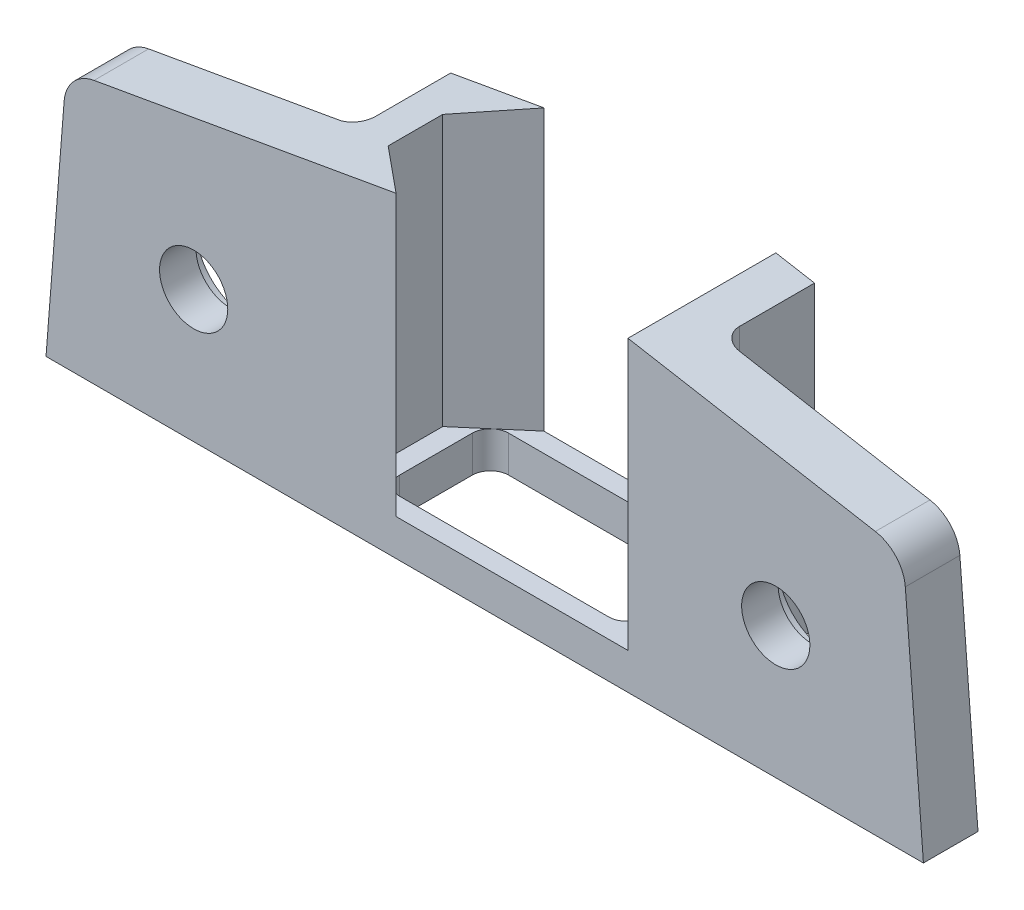
SolidWorks part; units mm, degrees
ref_plane "Front Plane" through (0, 0, 0) normal (0, 0, 1) x (1, 0, 0)
ref_plane "Top Plane" through (0, 0, 0) normal (0, 1, 0) x (1, 0, 0)
ref_plane "Right Plane" through (0, 0, 0) normal (1, 0, 0) x (0, 0, -1)
sketch "Sketch1" plane through (0, 0, 0) normal (0, 0, 1) x (1, 0, 0)
  line L0 (-24.457, 69.4319) -> (24.457, 69.4319)
  line L18 (24.457, 69.4319) -> (23.1215, 86.4007)
  line L19 (21.475, 88.2134) -> (0, 92)
  line L20 (0, 92) -> (-21.475, 88.2134)
  line L21 (-23.1215, 86.4007) -> (-24.457, 69.4319)
  line L22 (-24.5714, 68.9048) -> (-33.6515, 43.9576)
  line L23 (-33.4302, 42.1552) -> (-25.3419, 30.1639)
  line L24 (-25, 29.0455) -> (-25, -29.0455)
  line L25 (-25.3419, -30.1639) -> (-33.4302, -42.1552)
  line L26 (-33.6515, -43.9576) -> (-24.5714, -68.9048)
  line L27 (-24.457, -69.4319) -> (-23.1215, -86.4007)
  line L28 (-21.475, -88.2134) -> (0, -92)
  line L29 (0, -92) -> (21.475, -88.2134)
  line L30 (23.1215, -86.4007) -> (24.457, -69.4319)
  line L31 (24.5714, -68.9048) -> (33.6515, -43.9576)
  line L32 (33.4302, -42.1552) -> (25.3419, -30.1639)
  line L33 (25, -29.0455) -> (25, 29.0455)
  line L34 (25.3419, 30.1639) -> (33.4302, 42.1552)
  line L35 (33.6515, 43.9576) -> (24.5714, 68.9048)
  line L36 (24.457, 69.4319) -> (23.1215, 86.4007)
  line L37 (21.475, 88.2134) -> (0, 92)
  line L38 (0, 92) -> (-21.475, 88.2134)
  line L39 (-23.1215, 86.4007) -> (-24.457, 69.4319)
  circle A0 centre (-16, 81) radius 1.5 construction
  circle A1 centre (-16, 81) radius 1.5
  circle A2 centre (16, 81) radius 1.5 construction
  circle A3 centre (16, 81) radius 1.5
  arc A16 (24.457, 69.4319) -> (24.5714, 68.9048) centre (26.4508, 69.5889) ccw
  arc A17 (23.1215, 86.4007) -> (21.475, 88.2134) centre (21.1277, 86.2438) ccw
  arc A18 (-21.475, 88.2134) -> (-23.1215, 86.4007) centre (-21.1277, 86.2438) ccw
  arc A19 (-24.5714, 68.9048) -> (-24.457, 69.4319) centre (-26.4508, 69.5889) ccw
  arc A20 (-33.6515, 43.9576) -> (-33.4302, 42.1552) centre (-31.7721, 43.2736) ccw
  arc A21 (-25, 29.0455) -> (-25.3419, 30.1639) centre (-27, 29.0455) ccw
  arc A22 (-25.3419, -30.1639) -> (-25, -29.0455) centre (-27, -29.0455) ccw
  arc A23 (-33.4302, -42.1552) -> (-33.6515, -43.9576) centre (-31.7721, -43.2736) ccw
  arc A24 (-24.457, -69.4319) -> (-24.5714, -68.9048) centre (-26.4508, -69.5889) ccw
  arc A25 (-23.1215, -86.4007) -> (-21.475, -88.2134) centre (-21.1277, -86.2438) ccw
  arc A26 (21.475, -88.2134) -> (23.1215, -86.4007) centre (21.1277, -86.2438) ccw
  arc A27 (24.5714, -68.9048) -> (24.457, -69.4319) centre (26.4508, -69.5889) ccw
  arc A28 (33.6515, -43.9576) -> (33.4302, -42.1552) centre (31.7721, -43.2736) ccw
  arc A29 (25, -29.0455) -> (25.3419, -30.1639) centre (27, -29.0455) ccw
  arc A30 (25.3419, 30.1639) -> (25, 29.0455) centre (27, 29.0455) ccw
  arc A31 (33.4302, 42.1552) -> (33.6515, 43.9576) centre (31.7721, 43.2736) ccw
  arc A33 (23.1215, 86.4007) -> (21.475, 88.2134) centre (21.1277, 86.2438) ccw
  arc A34 (-21.475, 88.2134) -> (-23.1215, 86.4007) centre (-21.1277, 86.2438) ccw
  dimension "D1" = 0
extrude "Boss-Extrude1" add sketch "Sketch1" along normal blind 8.13
ref_plane "Plane1" through (0, 92, 0) normal (0, 1, 0) x (1, 0, 0)
sketch "Sketch2" plane through (0, 92, 0) normal (0, 1, 0) x (1, 0, 0)
  line L0 (0, -4.065) -> (24.457, -4.065) construction
  line L1 (0, -8.13) -> (0, 0) construction
  line L2 (24.457, -8.13) -> (24.457, 0) construction
  line L3 (21.475, -8.13) -> (0, -8.13) construction
  line L4 (-7.875, 0) -> (7.875, 0)
  line L5 (-7.875, 0) -> (-7.875, -8.13)
  line L6 (-7.875, -8.13) -> (7.875, -8.13)
  line L7 (7.875, 0) -> (7.875, -8.13)
  line L8 (-7.875, 0) -> (7.875, -8.13) construction
  line L9 (-7.875, -8.13) -> (7.875, 0) construction
  line L12 (-7.875, -2.565) -> (-4.875, 0)
  line L13 (-7.875, -5.565) -> (-4.875, -8.13)
  dimension "D1" = 15.75
  dimension "D4" = 12.75
  dimension "D5" = 3
extrude "Cut-Extrude1" cut sketch "Sketch2" against normal blind 16.25 contours L7 L4 L5 L6 region at (0.4396, 92, 4.065)
sketch "Sketch3" plane through (0, 75.75, 0) normal (0, 1, 0) x (1, 0, 0)
  line L0 (0, 0) -> (0, -8.13) construction
  line L1 (-4.875, -8.13) -> (7.875, -8.13) construction
  line L2 (0, -4.065) -> (24.457, -4.065) construction
  line L3 (24.457, -8.13) -> (24.457, 0) construction
  line L5 (-6.75, -1.065) -> (6.75, -1.065)
  line L6 (-6.75, -1.065) -> (-6.75, -7.065)
  line L7 (-6.75, -7.065) -> (6.75, -7.065)
  line L8 (6.75, -1.065) -> (6.75, -7.065)
  line L9 (-6.75, -1.065) -> (6.75, -7.065) construction
  line L10 (-6.75, -7.065) -> (6.75, -1.065) construction
  dimension "D1" = 13.5
  dimension "D2" = 6
extrude "Cut-Extrude2" cut sketch "Sketch3" against normal up to next
sketch "Sketch4" plane through (0, 0, 0) normal (0, 0, -1) x (-1, 0, 0)
  line L0 (-10, 90.2367) -> (-10, 69.4319)
  line L1 (0, 69.4319) -> (0, 91.1404) construction
  line L2 (10, 90.2367) -> (10, 69.4319)
  line L8 (21.475, 88.2134) -> (4.875, 91.1404)
  line L9 (4.875, 91.1404) -> (4.875, 75.75)
  line L10 (4.875, 75.75) -> (-7.875, 75.75)
  line L11 (4.875, 91.1404) -> (4.875, 75.75)
  line L12 (-7.875, 90.6114) -> (-21.475, 88.2134)
  line L13 (-23.1215, 86.4007) -> (-24.457, 69.4319)
  line L14 (-24.457, 69.4319) -> (24.457, 69.4319)
  line L15 (24.457, 69.4319) -> (23.1215, 86.4007)
  line L16 (21.475, 88.2134) -> (4.875, 91.1404)
  line L17 (-7.875, 75.75) -> (-7.875, 90.6114)
  line L18 (4.875, 75.75) -> (-7.875, 75.75)
  line L19 (-7.875, 75.75) -> (-7.875, 90.6114)
  line L20 (-7.875, 90.6114) -> (-21.475, 88.2134)
  line L21 (-23.1215, 86.4007) -> (-24.457, 69.4319)
  line L22 (-24.457, 69.4319) -> (24.457, 69.4319)
  line L23 (24.457, 69.4319) -> (23.1215, 86.4007)
  arc A2 (-21.475, 88.2134) -> (-23.1215, 86.4007) centre (-21.1277, 86.2438) ccw
  arc A3 (23.1215, 86.4007) -> (21.475, 88.2134) centre (21.1277, 86.2438) ccw
  arc A4 (-21.475, 88.2134) -> (-23.1215, 86.4007) centre (-21.1277, 86.2438) ccw
  arc A5 (23.1215, 86.4007) -> (21.475, 88.2134) centre (21.1277, 86.2438) ccw
  line M11 (21.475, 88.2134) -> (4.875, 91.1404)
  line M15 (-7.875, 90.6114) -> (-21.475, 88.2134)
  arc M16 (-21.475, 88.2134) -> (-23.1215, 86.4007) centre (-21.1277, 86.2438) ccw
  line M17 (-23.1215, 86.4007) -> (-24.457, 69.4319)
  line M18 (-24.457, 69.4319) -> (24.457, 69.4319)
  line M19 (24.457, 69.4319) -> (23.1215, 86.4007)
  arc M20 (23.1215, 86.4007) -> (21.475, 88.2134) centre (21.1277, 86.2438) ccw
  circle M21 centre (16, 81) radius 1.5
  circle M22 centre (-16, 81) radius 1.5
  dimension "D2" = 10
  dimension "D1" = 0
extrude "Cut-Extrude3" cut sketch "Sketch4" against normal offset from surface (5.13 mm away) 3 contours L0 M15 M16 M17 M18 M22 | L2 M11 M18 M19 M20 M21 region at (16.7394, 79.0217, 0) region at (-16.7394, 79.0217, 0) up to face at (17.5, 81, 8.13)
sketch "Sketch5" plane through (0, 0, 0) normal (0, 0, -1) x (-1, 0, 0)
  line L1 (4.875, 75.75) -> (-7.875, 75.75) construction
  line L2 (-24.457, 69.4319) -> (24.457, 69.4319)
  line L3 (-24.457, 69.4319) -> (-24.457, 73.75)
  line L4 (-24.457, 73.75) -> (24.457, 73.75)
  line L6 (24.457, 69.4319) -> (24.457, 73.75)
  dimension "D1" = 2
extrude "Cut-Extrude4" cut sketch "Sketch5" against normal up to next
fillet "Fillet1" radius 1 6 edges at (-6.75, 74.75, 1.065) (6.75, 74.75, 1.065) (6.75, 74.75, 7.065) (-6.75, 74.75, 7.065) (-10, 81.9934, 5.13) (10, 81.9934, 5.13)
sketch "Sketch8" plane through (0, 0, 5.13) normal (0, 0, -1) x (-1, 0, 0)
  circle A0 centre (16, 81) radius 1.875
  circle A1 centre (-16, 81) radius 1.875
  dimension "D1" = 3.75
extrude "Cut-Extrude6" cut sketch "Sketch8" against normal up to next
sketch "Sketch9" plane through (0, 0, 5.13) normal (0, 0, -1) x (-1, 0, 0)
  circle A0 centre (16, 81) radius 2.875
  circle A1 centre (-16, 81) radius 2.875
  dimension "D1" = 5.75
extrude "Cut-Extrude7" cut sketch "Sketch9" against normal offset from surface (1 mm away) 2 up to face at (17.875, 81, 8.13)
